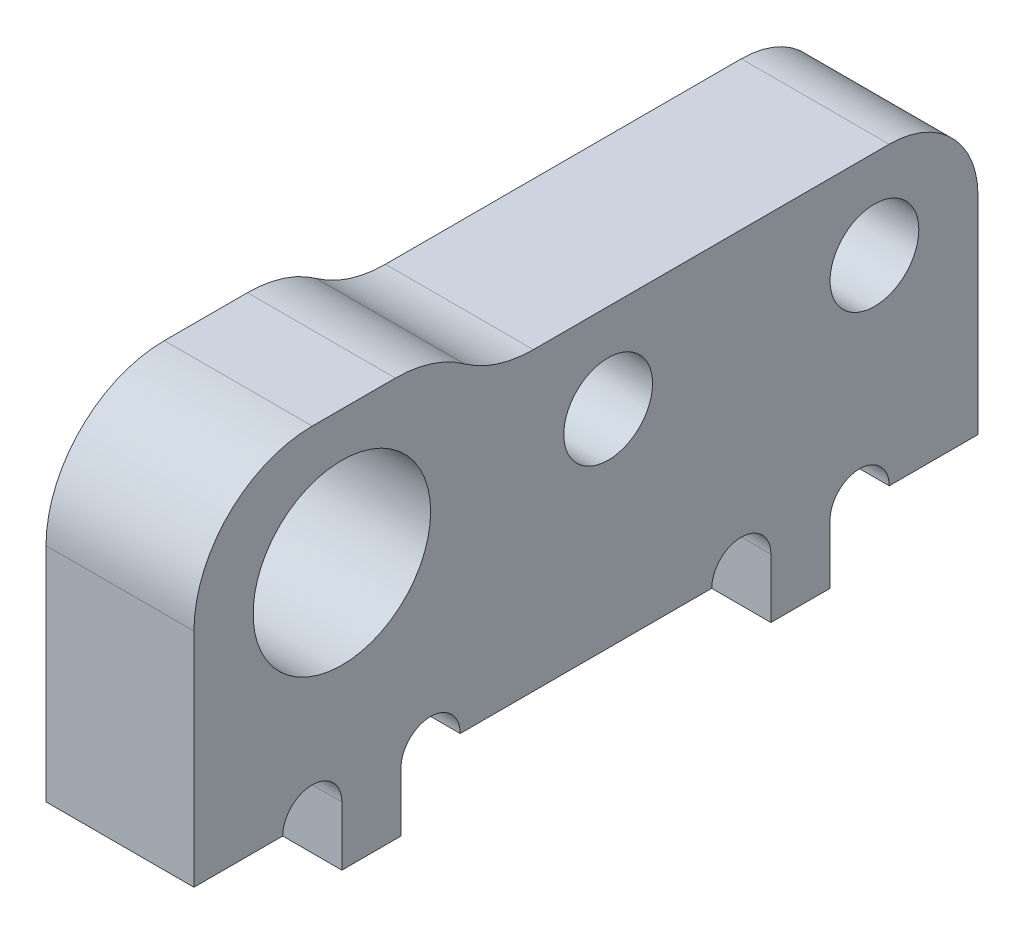
SolidWorks part; units mm, degrees
material "POM Acetal Copolymer"
ref_plane "Front Plane" through (0, 0, 0) normal (0, 0, 1) x (1, 0, 0)
ref_plane "Top Plane" through (0, 0, 0) normal (0, 1, 0) x (1, 0, 0)
ref_plane "Right Plane" through (0, 0, 0) normal (1, 0, 0) x (0, 0, -1)
ref_plane "pcb_bottom" through (0, -2, 0) normal (0, 1, 0) x (1, 0, 0)
ref_plane "shafts" through (0, 7, 0) normal (0, 1, 0) x (1, 0, 0)
ref_plane "motor_hole_top" through (0, 10, 0) normal (0, 1, 0) x (1, 0, 0)
ref_plane "gearbox_top" through (0, 11.5, 0) normal (0, 1, 0) x (1, 0, 0)
sketch "base" plane through (0, 0, 0) normal (0, 1, 0) x (1, 0, 0)
  line L1 (0, 0) -> (5, 0)
  line L2 (0, 0) -> (0, 26.5)
  line L3 (0, 26.5) -> (5, 26.5)
  line L4 (5, 0) -> (5, 26.5)
  dimension "D1" = 26.5
  dimension "D2" = 5
extrude "body" add sketch "base" along normal up to surface (11.5 mm away) up to plane "gearbox_top"
hole_wizard "Ø6.0mm motor" positions "Sketch2" profile "Sketch3" hole size "Ø6.0" standard "ANSI Metric"
sketch "Sketch2" plane through (5, 0, 0) normal (1, 0, 0) x (0, 0, -1)
  line L0 (0, 2.75) -> (0, -2.75) construction
  line L1 (2.75, 0) -> (-2.75, 0) construction
  point P0 (5, 7)
  dimension "D1" = 5
  dimension "D2" = 7
sketch "Sketch3" plane through (5, 7, -5) normal (0, 1, 0) x (0, 0, -1)
  line L0 (0, 0) -> (0, 6.8016)
  line L1 (0, 6.8016) -> (3, 4.999)
  line L2 (3, 4.999) -> (3, 0)
  line L5 (3, 0) -> (0, 0)
  line L10 (0, 6.8016) -> (-3, 4.999) construction
  line L11 (0, -6.35) -> (0, 107.95) construction
  dimension "Hole Dia." = 6
  dimension "Hole Depth" = 4.999
  dimension "Drill Angle" = 118
hole_wizard "Ø3.0mm bearings" positions "Sketch6" profile "Sketch8" hole size "Ø3.0" standard "ANSI Metric" end condition up to next
sketch "Sketch6" plane through (5, 0, 0) normal (1, 0, 0) x (0, 0, -1)
  point P0 (14, 7)
  point P2 (23, 7)
  dimension "D1" = 9
  dimension "D2" = 9
sketch "Sketch8" plane through (5, 7, -14) normal (0, 1, 0) x (0, 0, -1)
  line L0 (0, 0) -> (0, 5)
  line L1 (0, 5) -> (1.5, 5)
  line L2 (1.5, 5) -> (1.5, 0)
  line L5 (1.5, 0) -> (0, 0)
  line L11 (0, -6.35) -> (0, 107.95) construction
  dimension "Thru Hole Dia." = 3
  dimension "Thru Hole Depth" = 5
sketch "Sketch9" plane through (5, 0, 0) normal (1, 0, 0) x (0, 0, -1)
  line L0 (0, 11.5) -> (26.5, 11.5) construction
  line L1 (26.5, 11.5) -> (26.5, 0) construction
  line L2 (0, 11.5) -> (26.5, 11.5) construction
  line L3 (26.5, 11.5) -> (26.5, 0) construction
  line L4 (14, 8.5) -> (23, 8.5) construction
  line L5 (26.5, 11.5) -> (8.35, 11.5)
  line L6 (26.5, 11.5) -> (26.5, 10)
  line L7 (26.5, 10) -> (8.35, 10)
  line L8 (8.35, 11.5) -> (8.35, 10)
  circle A2 centre (14, 7) radius 1.5 construction
  dimension "D1" = 1.5
  dimension "D2" = 3.35
extrude "weight_saver" cut sketch "Sketch9" against normal up to next
fillet "Fillet2" radius 3 1 edges at (2.5, 10, -26.5)
fillet "Fillet1" radius 4 1 edges at (2.5, 11.5, 0)
fillet "Fillet4" radius 4 1 edges at (2.5, 10, -8.35)
fillet "Fillet5" radius 4 1 edges at (2.5, 11.5, -8.35)
sketch "Sketch10" plane through (0, 0, 0) normal (0, -1, 0) x (1, 0, 0)
  line L0 (0, 0) -> (5, 0) construction
  line L1 (0, -26.5) -> (0, 0) construction
  line L2 (5, 0) -> (5, -26.5) construction
  line L3 (0, 0) -> (5, 0) construction
  line L4 (0, -26.5) -> (0, 0) construction
  line L5 (5, 0) -> (5, -26.5) construction
  line L6 (5, -26.5) -> (0, -26.5) construction
  line L7 (5, -5) -> (0, -5)
  line L8 (5, -5) -> (5, -7)
  line L9 (5, -7) -> (0, -7)
  line L10 (0, -5) -> (0, -7)
  line L11 (5, -19.5) -> (0, -19.5)
  line L12 (5, -19.5) -> (5, -21.5)
  line L13 (5, -21.5) -> (0, -21.5)
  line L14 (0, -19.5) -> (0, -21.5)
  dimension "D1" = 2
  dimension "D2" = 2
  dimension "D3" = 5
  dimension "D4" = 5
extrude "mounting" add sketch "Sketch10" along normal up to surface (2 mm away) up to plane "pcb_bottom"
sketch "mounting_undercut" plane through (5, 0, 0) normal (1, 0, 0) x (0, 0, -1)
  line L0 (21.5, 0) -> (26.5, 0) construction
  line L1 (21.5, -2) -> (21.5, 0) construction
  line L2 (19.5, -2) -> (19.5, 0) construction
  line L3 (7, -2) -> (7, 0) construction
  line L4 (7, 0) -> (19.5, 0) construction
  line L5 (0, 0) -> (5, 0) construction
  line L6 (5, -2) -> (5, 0) construction
  line L7 (21.5, 0) -> (26.5, 0) construction
  line L8 (21.5, -2) -> (21.5, 0) construction
  line L9 (19.5, -2) -> (19.5, 0) construction
  line L10 (7, -2) -> (7, 0) construction
  line L11 (7, 0) -> (19.5, 0) construction
  line L12 (0, 0) -> (5, 0) construction
  line L13 (5, -2) -> (5, 0) construction
  line L14 (3, 0) -> (5, 0)
  line L15 (7, 0) -> (9, 0)
  line L16 (17.5, 0) -> (19.5, 0)
  line L17 (21.5, 0) -> (23.5, 0)
  arc A0 (5, 0) -> (3, 0) centre (4, 0) ccw
  arc A1 (7, 0) -> (9, 0) centre (8, 0) cw
  arc A2 (19.5, 0) -> (17.5, 0) centre (18.5, 0) ccw
  arc A3 (21.5, 0) -> (23.5, 0) centre (22.5, 0) cw
  dimension "D1" = 2
  dimension "D2" = 2
  dimension "D3" = 2
  dimension "D4" = 2
extrude "mountin_undercut" cut sketch "mounting_undercut" against normal up to next
sketch "Sketch13" plane through (0, 0, 0) normal (-1, 0, 0) x (0, 0, 1)
  circle A0 centre (-5, 7) radius 4
  circle A1 centre (-5, 7) radius 3 construction
  circle A2 centre (-5, 7) radius 3
  dimension "D1" = 1
extrude "motor_holder" [suppressed] add sketch "Sketch13" along normal blind 1
hole_wizard "Ø4.0mm Dowel Hole2" positions "Sketch14" profile "Sketch15" hole size "Ø4.0" standard "DIN"
sketch "Sketch14" plane through (0, 0, 0) normal (-1, 0, 0) x (0, 0, 1)
  point P0 (-23, 7)
sketch "Sketch15" plane through (0, 7, -23) normal (0, 1, 0) x (0, 0, 1)
  line L0 (0, 0) -> (0, 1.5)
  line L1 (0, 1.5) -> (2.25, 1.5)
  line L2 (2.25, 1.5) -> (2.25, 0)
  line L5 (2.25, 0) -> (0, 0)
  line L10 (0, 1.5) -> (-2.25, 1.5) construction
  line L11 (0, -6.35) -> (0, 107.95) construction
  dimension "Hole Dia." = 4.5
  dimension "Hole Depth" = 1.5
  dimension "Drill Angle" = 180
sketch "Skizze1" plane through (5, 0, 0) normal (1, 0, 0) x (0, 0, -1)
  circle A0 centre (23, 7) radius 2
  circle A1 centre (23, 7) radius 1.5 construction
  circle A2 centre (23, 7) radius 1.5
  dimension "D1" = 4
move or copy body "Körper-Verschieben/Kopieren1" [suppressed] bodies to move or copy 111
